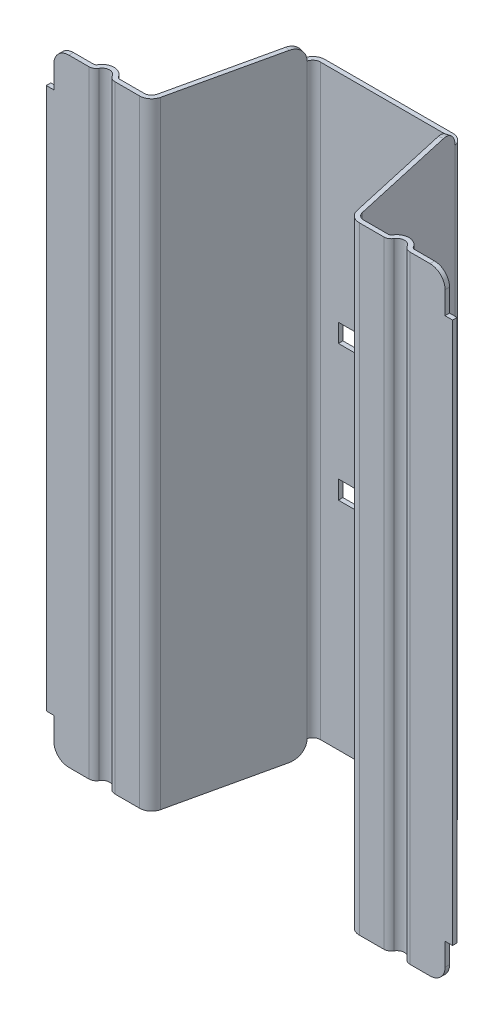
SolidWorks part; units mm, degrees
material "1023 Carbon Steel Sheet (SS)"
ref_plane "Front Plane" through (0, 0, 0) normal (0, 0, 1) x (1, 0, 0)
ref_plane "Top Plane" through (0, 0, 0) normal (0, 1, 0) x (1, 0, 0)
ref_plane "Right Plane" through (0, 0, 0) normal (1, 0, 0) x (0, 0, -1)
sketch "Sketch1" plane through (0, 0, 0) normal (0, 1, 0) x (1, 0, 0)
  line L0 (-55, 0) -> (55, 0) construction
  line L1 (0, -55) -> (0, 55) construction
  line L2 (13.5, 0) -> (10.666, 0)
  line L3 (8.934, 0) -> (7.3, 0)
  line L4 (6.5194, 0.625) -> (4.7379, 8.5694)
  line L5 (4.25, 8.96) -> (-4.25, 8.96)
  line L6 (-4.7379, 8.5694) -> (-6.5194, 0.625)
  line L7 (-7.3, 0) -> (-8.934, 0)
  line L8 (-10.666, 0) -> (-13.5, 0)
  circle A0 centre (-9.8, 0) radius 0.5 construction
  circle A1 centre (9.8, 0) radius 0.5 construction
  arc A2 (10.233, 0.25) -> (9.367, 0.25) centre (9.8, 0) ccw
  arc A3 (-9.367, 0.25) -> (-10.233, 0.25) centre (-9.8, 0) ccw
  arc A4 (-6.5194, 0.625) -> (-7.3, 0) centre (-7.3, 0.8) cw
  arc A5 (7.3, 0) -> (6.5194, 0.625) centre (7.3, 0.8) cw
  arc A6 (-4.7379, 8.5694) -> (-4.25, 8.96) centre (-4.25, 8.46) cw
  arc A7 (4.25, 8.96) -> (4.7379, 8.5694) centre (4.25, 8.46) cw
  arc A8 (-8.934, 0) -> (-9.367, 0.25) centre (-8.934, 0.5) cw
  arc A9 (-10.666, 0) -> (-10.233, 0.25) centre (-10.666, 0.5) ccw
  arc A10 (8.934, 0) -> (9.367, 0.25) centre (8.934, 0.5) ccw
  arc A11 (10.666, 0) -> (10.233, 0.25) centre (10.666, 0.5) cw
  point P22 (-6.6595, 0)
  point P25 (6.6595, 0)
  point P28 (-4.6503, 8.96)
  point P31 (4.6503, 8.96)
  point P34 (-9.3, 0)
  point P37 (-10.3, 0)
  point P40 (9.3, 0)
  point P43 (10.3, 0)
  dimension "D3" = 1
  dimension "D5" = 0.8
  dimension "D6" = 0.8
  dimension "D8" = 0.5
  dimension "D11" = 0.5
  dimension "D1" = 19.6
  dimension "D2" = 9.8
  dimension "D4" = 8.96
  dimension "D7" = 8.5
  dimension "D9" = 14.6
  dimension "D10" = 27
extrude "Extrude-Thin1" add sketch "Sketch1" along normal mid plane 41 thin thin type one direction wall 0.3
sketch "Sketch2" plane through (0, 0, 0) normal (0, 0, 1) x (1, 0, 0)
  line L0 (-13.5, 18) -> (-13, 18)
  line L1 (-13.5, 20.5) -> (-13.5, -20.5) construction
  line L2 (-13, 18) -> (-13, 19.5)
  line L3 (-13.5, -18) -> (-13, -18)
  line L4 (-12, 20.5) -> (0, 20.5)
  line L5 (4.25, 20.5) -> (-4.25, 20.5) construction
  line L6 (-13, -18) -> (-13, -19.5)
  line L7 (-10.666, -20.5) -> (-13.5, -20.5) construction
  line L8 (-12, -20.5) -> (12, -20.5)
  line L9 (0, 20.5) -> (12, 20.5)
  line L10 (13.5, -20.5) -> (10.666, -20.5) construction
  line L11 (13, 19.5) -> (13, 18)
  line L12 (13, 18) -> (13.5, 18)
  line L13 (13.5, 20.5) -> (13.5, -20.5) construction
  line L14 (13.5, 18) -> (13.5, 21.5)
  line L15 (13.5, 21.5) -> (-13.5, 21.5)
  line L16 (-13.5, 21.5) -> (-13.5, 18)
  line L17 (13, -19.5) -> (13, -18)
  line L18 (13, -18) -> (13.5, -18)
  line L19 (13.5, -18) -> (13.5, -21.5)
  line L20 (13.5, -21.5) -> (-13.5, -21.5)
  line L21 (-13.5, -21.5) -> (-13.5, -18)
  arc A0 (12, 20.5) -> (13, 19.5) centre (12, 19.5) cw
  arc A1 (-13, 19.5) -> (-12, 20.5) centre (-12, 19.5) cw
  arc A2 (-12, -20.5) -> (-13, -19.5) centre (-12, -19.5) cw
  arc A3 (13, -19.5) -> (12, -20.5) centre (12, -19.5) cw
  point P20 (-13, 20.5)
  point P35 (-13, -20.5)
  point P38 (13, -20.5)
  dimension "D6" = 1
  dimension "D3" = 1
  dimension "D1" = 2.5
  dimension "D2" = 26
  dimension "D4" = 1
  dimension "D5" = 1
extrude "Extrude1" cut sketch "Sketch2" against normal blind 41
sketch "Sketch3" plane through (0, 20.5, 0) normal (0, 1, 0) x (1, 0, 0)
  line L0 (-5.0306, 8.635) -> (-4.7379, 8.5694)
  line L1 (-4.7379, 8.5694) -> (4.7379, 8.5694)
  line L2 (4.7379, 8.5694) -> (5.0306, 8.635)
  line L3 (5.0306, 8.635) -> (5.0306, 9.5694)
  line L4 (5.0306, 9.5694) -> (-5.0306, 9.5694)
  line L5 (-5.0306, 9.5694) -> (-5.0306, 8.635)
  dimension "D1" = 1
extrude "Extrude2" cut sketch "Sketch3" against normal blind 1
fillet "Fillet1" radius 1 2 edges at (-4.8842, 20.5, -8.6022) (4.8842, 20.5, -8.6022)
sketch "Sketch4" plane through (0, -20.5, 0) normal (0, -1, 0) x (1, 0, 0)
  line L0 (-4.7379, -8.5694) -> (-5.0306, -8.635)
  line L1 (-5.0306, -8.635) -> (-5.0306, -10.26)
  line L2 (-5.0306, -10.26) -> (5.0306, -10.26)
  line L3 (5.0306, -10.26) -> (5.0306, -8.635)
  line L4 (5.0306, -8.635) -> (4.7379, -8.5694)
  line L5 (6.5194, -0.625) -> (4.7379, -8.5694) construction
  line L6 (4.7379, -8.5694) -> (-4.7379, -8.5694)
  line L7 (4.25, -9.26) -> (-4.25, -9.26) construction
  arc A0 (4.25, -8.96) -> (4.7379, -8.5694) centre (4.25, -8.46) ccw construction
  dimension "D1" = 1
extrude "Extrude3" cut sketch "Sketch4" against normal blind 1
fillet "Fillet2" radius 1 2 edges at (4.8842, -20.5, -8.6022) (-4.8842, -20.5, -8.6022)
sketch "Sketch5" plane through (0, 0, 0) normal (0, 0, 1) x (1, 0, 0)
  line L1 (-3.05, 5.12) -> (3.05, 5.12)
  line L2 (-3.05, 5.12) -> (-3.05, 3.9)
  line L3 (-3.05, 3.9) -> (3.05, 3.9)
  line L4 (3.05, 5.12) -> (3.05, 3.9)
  line L5 (-3.05, -3.9) -> (3.05, -3.9)
  line L6 (-3.05, -3.9) -> (-3.05, -5.12)
  line L7 (-3.05, -5.12) -> (3.05, -5.12)
  line L8 (3.05, -3.9) -> (3.05, -5.12)
  line L9 (0, -5.093) -> (0, 5.093) construction
  line L10 (5.093, 0) -> (-5.093, 0) construction
  dimension "D1" = 6.1
  dimension "D2" = 3.05
  dimension "D3" = 1.22
  dimension "D4" = 7.8
  dimension "D5" = 3.9
extrude "Extrude4" cut sketch "Sketch5" against normal blind 45.5
